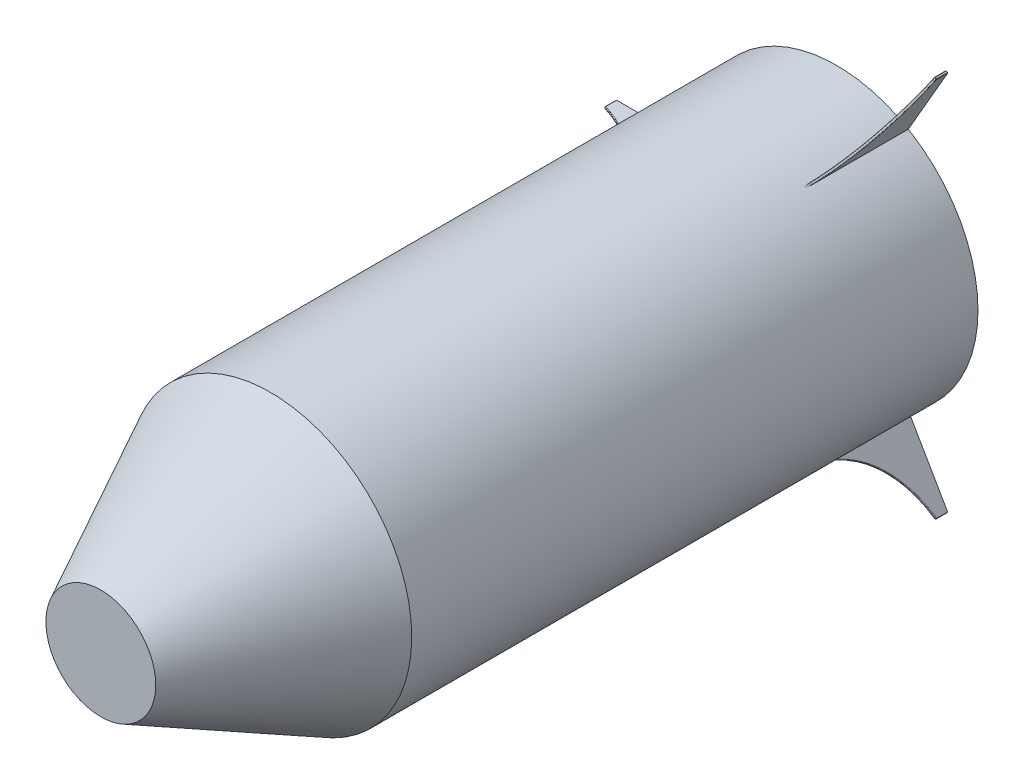
SolidWorks part; units mm, degrees
material "6061-T6 (SS)"
ref_plane "Front Plane" through (0, 0, 0) normal (0, 0, 1) x (1, 0, 0)
ref_plane "Top Plane" through (0, 0, 0) normal (0, 1, 0) x (1, 0, 0)
ref_plane "Right Plane" through (0, 0, 0) normal (1, 0, 0) x (0, 0, -1)
sketch "Sketch1" plane through (0, 0, 0) normal (0, 0, 1) x (1, 0, 0)
  circle A0 centre (0, 0) radius 3810
  dimension "D1" = 7620
extrude "Boss-Extrude1" add sketch "Sketch1" along normal blind 25.4
sketch "Sketch2" plane through (0, 0, 25.4) normal (0, 0, 1) x (1, 0, 0)
  circle A0 centre (0, 0) radius 3810
  circle A1 centre (0, 0) radius 3803.65
  dimension "D1" = 6.35
  dimension "D2" = 7620
extrude "Boss-Extrude2" add sketch "Sketch2" along normal blind 15240
ref_plane "Plane1" through (0, 0, 15265.4) normal (0, 0, 1) x (1, 0, 0)
sketch "Sketch3" plane through (0, 0, 15265.4) normal (0, 0, 1) x (1, 0, 0)
  circle A0 centre (0, 0) radius 3048
  circle A1 centre (0, 0) radius 3810
  dimension "D1" = 7620
  dimension "D2" = 6096
extrude "Boss-Extrude4" add sketch "Sketch3" along normal blind 4572 draft 27 contours A1
extrude "Cut-Extrude2" cut sketch "Sketch3<5>" along normal blind 4267.2 draft 27 contours A0 region at (0, 0, 15265.4)
sketch "Sketch3<5>" plane through (0, 0, 15265.4) normal (0, 0, 1) x (1, 0, 0) same geometry as "Sketch3"
sketch "Sketch4" plane through (0, 0, 0) normal (0, 1, 0) x (1, 0, 0)
  line L0 (-3810, 0) -> (-5943.6, 0)
  line L1 (-5943.6, 0) -> (-5943.6, -304.8)
  line L2 (-7162.8, -125.6018) -> (-7162.8, -5360.7982) construction
  line L3 (-3810, 0) -> (-3810, -15265.4) construction
  line L4 (-3810, -2743.2) -> (-3810, 0)
  line L6 (-10515.6, -2743.2) -> (-3810, -2743.2) construction
  ellipse E0 centre (-7162.8, -2743.2) end of major axis (-3810, -2743.2) minor radius 2617.5982 (-5943.6, -304.8) -> (-3810, -2743.2) cw
  dimension "D1" = 304.8
  dimension "D2" = 2133.6
  dimension "D3" = 3352.8
  dimension "D4" = 2743.2
extrude "Boss-Extrude5" add sketch "Sketch4" along normal blind 30.48 and the other way blind 30.48 separate body
fillet "Fillet1" radius 15.24 5 edges at (-5943.6, 0, 304.8) (-5943.6, 30.48, 152.4) (-5943.6, -30.48, 152.4) (-4394.3165, 30.48, 1266.6755) (-4394.3165, -30.48, 1266.6755)
pattern_circular "CirPattern1" count 3 over 360 about axis through (0, 0, 0) along (0, 0, 1) of bodies 108
